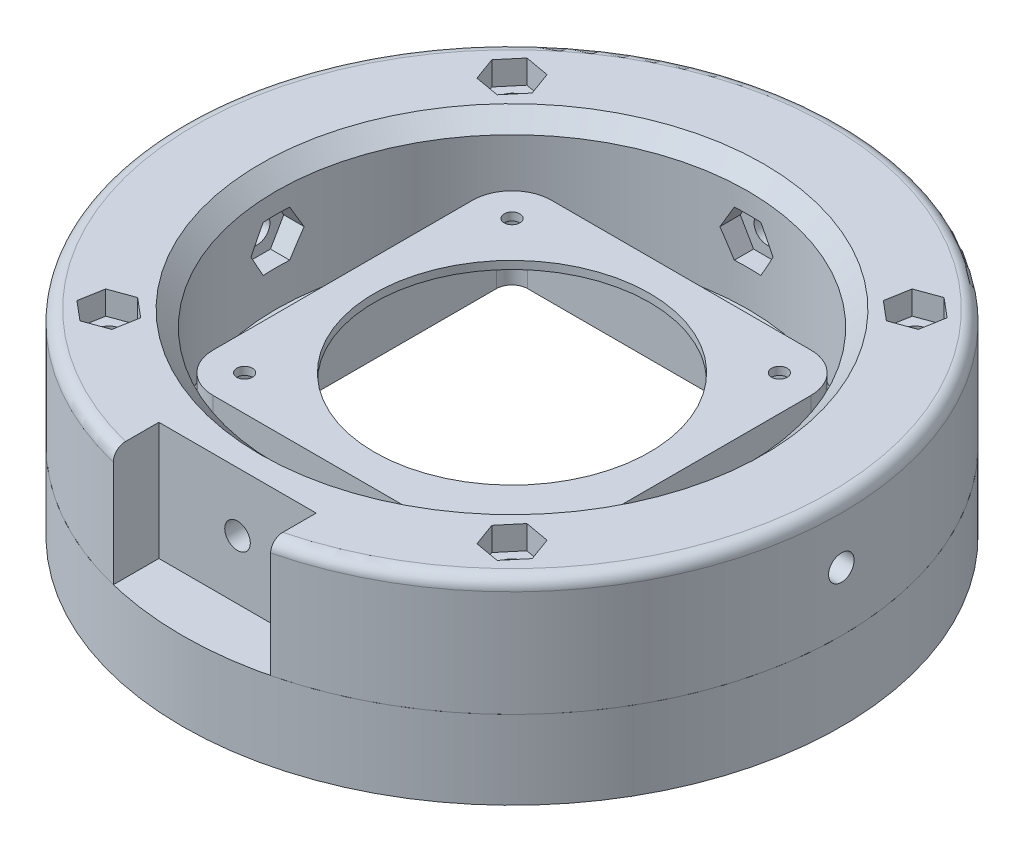
SolidWorks part; units mm, degrees
ref_plane "Front" through (0, 0, 0) normal (0, 0, 1) x (1, 0, 0)
ref_plane "Top" through (0, 0, 0) normal (0, 1, 0) x (1, 0, 0)
ref_plane "Right" through (0, 0, 0) normal (1, 0, 0) x (0, 0, -1)
sketch "Sketch1" plane through (0, 0, 0) normal (0, 1, 0) x (1, 0, 0)
  circle A0 centre (0, 0) radius 41.9
  dimension "D1" = 83.8
extrude "Top-Part" add sketch "Sketch1" along normal blind 15
sketch "Sketch2" plane through (0, 15, 0) normal (0, 1, 0) x (1, 0, 0)
  circle A0 centre (0, 0) radius 30
  dimension "D1" = 60
extrude "Cut-Extrude1" cut sketch "Sketch2" against normal blind 20
fillet "Fillet1" radius 1.5 1 edges at (0, 15, 41.9)
chamfer "Chamfer1" distance 2 angle 45 1 edges at (0, 15, 30)
sketch "Sketch8" plane through (0, 15, 0) normal (0, 1, 0) x (1, 0, 0)
  line L0 (0, 0) -> (0, 52.711) construction
  line L1 (25.0832, 22.5168) -> (28.0563, 23.5989)
  line L8 (0, 0) -> (-43.3951, 43.3951) construction
  line L9 (-25.6326, 25.6326) -> (-25.6326, 34.5059) construction
  line L10 (-22.5168, 25.0832) -> (-23.5989, 28.0563)
  line L11 (-23.5989, 28.0563) -> (-26.7147, 28.6057)
  line L12 (-26.7147, 28.6057) -> (-28.7485, 26.182)
  line L13 (-28.7485, 26.182) -> (-27.6663, 23.2089)
  line L14 (-27.6663, 23.2089) -> (-24.5505, 22.6595)
  line L15 (-24.5505, 22.6595) -> (-22.5168, 25.0832)
  line L16 (28.0563, 23.5989) -> (28.6057, 26.7147)
  line L17 (28.6057, 26.7147) -> (26.182, 28.7485)
  line L18 (26.182, 28.7485) -> (23.2089, 27.6663)
  line L19 (23.2089, 27.6663) -> (22.6595, 24.5505)
  line L20 (22.6595, 24.5505) -> (25.0832, 22.5168)
  line L21 (0, 0) -> (43.3951, 43.3951) construction
  line L23 (22.5168, -25.0832) -> (23.5989, -28.0563)
  line L24 (23.5989, -28.0563) -> (26.7147, -28.6057)
  line L25 (26.7147, -28.6057) -> (28.7485, -26.182)
  line L26 (28.7485, -26.182) -> (27.6663, -23.2089)
  line L27 (27.6663, -23.2089) -> (24.5505, -22.6595)
  line L28 (24.5505, -22.6595) -> (22.5168, -25.0832)
  line L29 (0, 0) -> (43.3951, -43.3951) construction
  line L31 (-25.0832, -22.5168) -> (-28.0563, -23.5989)
  line L32 (-28.0563, -23.5989) -> (-28.6057, -26.7147)
  line L33 (-28.6057, -26.7147) -> (-26.182, -28.7485)
  line L34 (-26.182, -28.7485) -> (-23.2089, -27.6663)
  line L35 (-23.2089, -27.6663) -> (-22.6595, -24.5505)
  line L36 (-22.6595, -24.5505) -> (-25.0832, -22.5168)
  line L37 (0, 0) -> (-43.3951, -43.3951) construction
  line L39 (-25.6326, 25.6326) -> (-27.9138, 12.6954) construction
  circle A0 centre (0, 0) radius 36.25 construction
  circle A1 centre (25.6326, 25.6326) radius 2.74 construction
  circle A2 centre (-25.6326, 25.6326) radius 2.74 construction
  circle A3 centre (25.6326, -25.6326) radius 2.74 construction
  circle A4 centre (-25.6326, -25.6326) radius 2.74 construction
  circle A5 centre (-25.6326, 25.6326) radius 1.625
  circle A6 centre (25.6326, 25.6326) radius 1.625
  circle A7 centre (25.6326, -25.6326) radius 1.625
  circle A8 centre (-25.6326, -25.6326) radius 1.625
  point P8 (25.6326, 25.6326)
  point P10 (28.331, 25.1568)
  point P18 (-25.6326, 25.6326)
  point P20 (-25.1568, 28.331)
  point P36 (25.6326, -25.6326)
  point P38 (25.1568, -28.331)
  point P50 (-25.6326, -25.6326)
  point P52 (-28.331, -25.1568)
  point P63 (0, 0)
  point P69 (-27.8231, 23.2366)
  dimension "D1" = 72.5
  dimension "D5" = 3.25
  dimension "D2" = 4
  dimension "D3" = 45
  dimension "D4" = 10
  dimension "D6" = 5.75
extrude "Cut-Extrude8" cut sketch "Sketch8<7>" against normal blind 3
sketch "Sketch8<7>" plane through (0, 15, 0) normal (0, 1, 0) x (1, 0, 0) same geometry as "Sketch8"
extrude "Cut-Extrude7" cut sketch "Sketch8" against normal through all contours A5 | A6 | A7 | A8
sketch "Sketch13" plane through (0, 0, 0) normal (0, -1, 0) x (1, 0, 0)
  line L0 (0, 0) -> (0, 66.0162) construction
  line L1 (-10, 35.5191) -> (-10, 40.6892)
  line L2 (10, 35.5191) -> (10, 40.6892)
  line L3 (-10, 40.6892) -> (10, 35.5191) construction
  line L4 (10, 40.6892) -> (-10, 35.5191) construction
  circle A0 centre (0, 0) radius 41.9 construction
  arc A1 (10, 40.6892) -> (-10, 40.6892) centre (0, 0) ccw
  arc A2 (10, 35.5191) -> (-10, 35.5191) centre (0, 0) ccw
  point P6 (0, 38.1042)
  point P10 (0, 36.9)
  point P12 (0, 41.9)
  dimension "D1" = 10
  dimension "D3" = 5
extrude "Cut-Extrude11" cut sketch "Sketch13" against normal through all
ref_plane "Plane2" through (0, 0, 41.9) normal (0, 0, 1) x (1, 0, 0)
ref_plane "Plane3" through (0, 0, 32.4) normal (0, 0, 1) x (1, 0, 0)
sketch "Sketch15" plane through (0, 0, 32.4) normal (0, 0, 1) x (1, 0, 0)
  line L0 (0, -23.0183) -> (0, 33.1182) construction
  circle A1 centre (0, 7.5) radius 1.625
  point P11 (0, 7.5)
  dimension "D3" = 3.25
  dimension "D1" = 7.5
extrude "Cut-Extrude14" cut sketch "Sketch15" against normal blind 10 and the other way blind 10
sketch "Sketch16" plane through (0, 0, 32.4) normal (0, 0, 1) x (1, 0, 0)
  line L0 (0, 0) -> (0, 26.985) construction
  line L2 (3.3775, 7.5) -> (1.6887, 10.425)
  line L3 (1.6887, 10.425) -> (-1.6887, 10.425)
  line L4 (-1.6887, 10.425) -> (-3.3775, 7.5)
  line L5 (-3.3775, 7.5) -> (-1.6887, 4.575)
  line L6 (-1.6887, 4.575) -> (1.6887, 4.575)
  line L7 (1.6887, 4.575) -> (3.3775, 7.5)
  circle A0 centre (0, 7.5) radius 2.925 construction
  point P4 (0, 4.575)
  point P13 (0, 10.425)
  dimension "D1" = 5.85
  dimension "D2" = 7.5
extrude "Cut-Extrude15" cut sketch "Sketch16" against normal blind 10
pattern_circular "CirPattern1" count 4 over 360 about axis through (0, 0, 0) along (0, 1, 0) of "Cut-Extrude14"
pattern_circular "CirPattern2" count 4 every 90 about axis through (0, 0, 0) along (0, 1, 0) of "Cut-Extrude15"
sketch "Sketch3" plane through (0, 0, 0) normal (0, -1, 0) x (1, 0, 0)
  circle A0 centre (0, 0) radius 41.9
  dimension "D1" = 83.8
extrude "Bottom-Part" add sketch "Sketch3" along normal blind 20 separate body
ref_plane "Plane1" through (0, -1.5, 0) normal (0, 1, 0) x (1, 0, 0)
sketch "Sketch6" plane through (0, -1.5, 0) normal (0, 1, 0) x (1, 0, 0)
  line L0 (0, 0) -> (-97.4577, 0) construction
  line L5 (-37.9, 0) -> (-41.9, 0) construction
  circle A0 centre (0, 0) radius 37.9
  circle A1 centre (0, 0) radius 41.9 construction
  circle A2 centre (0, 0) radius 41.9 construction
  point P6 (-37.9, 0)
  point P9 (-41.9, 0)
  dimension "D1" = 4
extrude "Cut-Extrude3" cut sketch "Sketch6" against normal through all
sketch "ｽｹｯﾁ1" plane through (0, 0, 0) normal (0, 1, 0) x (1, 0, 0)
  line L3 (21.5, -21.5) -> (-21.5, -21.5)
  line L4 (21.5, -21.5) -> (21.5, 21.5)
  line L5 (21.5, 21.5) -> (-21.5, 21.5)
  line L6 (-21.5, -21.5) -> (-21.5, 21.5)
  line L7 (21.5, -21.5) -> (-21.5, 21.5) construction
  line L8 (21.5, 21.5) -> (-21.5, -21.5) construction
  point P2 (0, 0)
  dimension "D1" = 43
extrude "ﾎﾞｽ - 押し出し1" add sketch "ｽｹｯﾁ1" along normal blind 8
fillet "ﾌｨﾚｯﾄ1" radius 5 4 edges at (21.5, 4, -21.5) (-21.5, 4, -21.5) (-21.5, 4, 21.5) (21.5, 4, 21.5)
sketch "Sketch7" plane through (0, -1.5, 0) normal (0, 1, 0) x (1, 0, 0)
  circle A0 centre (0, 0) radius 17.5
  circle A1 centre (17, -17) radius 1
  circle A2 centre (-17, -17) radius 1
  circle A3 centre (-17, 17) radius 1
  circle A4 centre (17, 17) radius 1
  dimension "D1" = 35
  dimension "D2" = 2
extrude "Cut-Extrude4" cut sketch "Sketch7" against normal through all and the other way through all
sketch "Sketch12" plane through (0, -1.5, 0) normal (0, -1, 0) x (1, 0, 0)
  line L1 (19.75, -19.75) -> (-19.75, -19.75)
  line L2 (19.75, -19.75) -> (19.75, 19.75)
  line L3 (19.75, 19.75) -> (-19.75, 19.75)
  line L4 (-19.75, -19.75) -> (-19.75, 19.75)
  line L5 (19.75, -19.75) -> (-19.75, 19.75) construction
  line L6 (19.75, 19.75) -> (-19.75, -19.75) construction
  point P0 (0, 0)
  dimension "D1" = 39.5
extrude "Cut-Extrude10" cut sketch "Sketch12" against normal blind 8.5
fillet "Fillet3" radius 2 4 edges at (-19.75, 2.75, -19.75) (-19.75, 2.75, 19.75) (19.75, 2.75, -19.75) (19.75, 2.75, 19.75)
sketch "Sketch17" plane through (0, -1.5, 0) normal (0, -1, 0) x (1, 0, 0)
  circle A0 centre (25.6326, -25.6326) radius 1.625 construction
  circle A1 centre (-25.6326, -25.6326) radius 1.625 construction
  circle A2 centre (25.6326, 25.6326) radius 1.625 construction
  circle A3 centre (-25.6326, 25.6326) radius 1.625 construction
  circle A4 centre (25.6326, -25.6326) radius 1.625
  circle A5 centre (-25.6326, -25.6326) radius 1.625
  circle A6 centre (25.6326, 25.6326) radius 1.625
  circle A7 centre (-25.6326, 25.6326) radius 1.625
extrude "Cut-Extrude16" cut sketch "Sketch17" against normal through all
sketch "Sketch18" plane through (0, -1.5, 0) normal (0, -1, 0) x (1, 0, 0)
  circle A0 centre (-25.6326, 25.6326) radius 3
  circle A1 centre (25.6326, 25.6326) radius 3
  circle A2 centre (25.6326, -25.6326) radius 3
  circle A3 centre (-25.6326, -25.6326) radius 3
  dimension "D1" = 6
extrude "Cut-Extrude17" cut sketch "Sketch18" along normal through all
sketch "Sketch19" plane through (0, -1.5, 0) normal (0, -1, 0) x (1, 0, 0)
  line L0 (-6, 33) -> (-6, 37.4221)
  line L1 (6, 33) -> (6, 37.4221)
  line L2 (33, 6) -> (37.4221, 6)
  line L3 (33, -6) -> (37.4221, -6)
  line L4 (6, -33) -> (6, -37.4221)
  line L5 (-6, -33) -> (-6, -37.4221)
  line L6 (-33, -6) -> (-37.4221, -6)
  line L7 (-33, 6) -> (-37.4221, 6)
  arc A0 (-6, 33) -> (6, 33) centre (0, 33) ccw
  arc A1 (24.9276, 28.5486) -> (-24.9276, 28.5486) centre (0, 0) ccw construction
  arc A2 (24.9276, 28.5486) -> (-24.9276, 28.5486) centre (0, 0) ccw construction
  arc A3 (6, 37.4221) -> (-6, 37.4221) centre (0, 0) ccw
  arc A4 (37.4221, -6) -> (37.4221, 6) centre (0, 0) ccw
  arc A5 (33, 6) -> (33, -6) centre (33, 0) ccw
  arc A6 (-6, -37.4221) -> (6, -37.4221) centre (0, 0) ccw
  arc A7 (6, -33) -> (-6, -33) centre (0, -33) ccw
  arc A8 (-37.4221, 6) -> (-37.4221, -6) centre (0, 0) ccw
  arc A9 (-33, -6) -> (-33, 6) centre (-33, 0) ccw
  circle A10 centre (0, 33) radius 2.75
  circle A11 centre (33, 0) radius 2.75
  circle A12 centre (0, -33) radius 2.75
  circle A13 centre (-33, 0) radius 2.75
  dimension "D1" = 12
  dimension "D4" = 4
  dimension "D5" = 5.5
  dimension "D2" = 33
  dimension "D3" = 4
extrude "Boss-Extrude1" add sketch "Sketch19" along normal up to surface (18.5 mm away) up to face at (0, -20, 0)
sketch "Sketch20" plane through (0, -20, 0) normal (0, -1, 0) x (1, 0, 0)
  line L1 (-43.8995, -46.5498) -> (43.8995, -46.5498)
  line L2 (-43.8995, -46.5498) -> (-43.8995, 46.5498)
  line L3 (-43.8995, 46.5498) -> (43.8995, 46.5498)
  line L4 (43.8995, -46.5498) -> (43.8995, 46.5498)
  line L5 (-43.8995, -46.5498) -> (43.8995, 46.5498) construction
  line L6 (-43.8995, 46.5498) -> (43.8995, -46.5498) construction
  point P0 (0, 0)
extrude "Cut-Extrude18" cut sketch "Sketch20" against normal blind 10
sketch "Sketch21" plane through (0, 15, 0) normal (0, 1, 0) x (1, 0, 0)
  line L1 (-10, -34.9) -> (10, -34.9)
  line L2 (-10, -34.9) -> (-10, -43.5518)
  line L3 (-10, -43.5518) -> (10, -43.5518)
  line L4 (10, -34.9) -> (10, -43.5518)
  dimension "D1" = 34.9
extrude "Cut-Extrude19" cut sketch "Sketch21" against normal up to surface (15 mm away) up to face at (-25.6326, 0, -27.2576)
